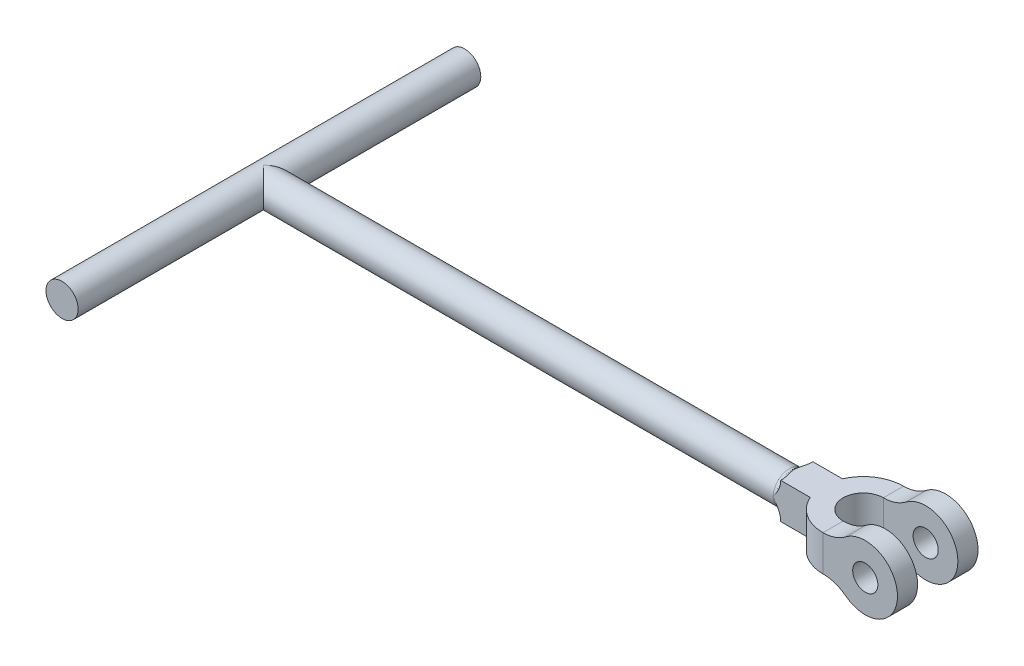
SolidWorks part; units mm, degrees
ref_plane "Front Plane" through (0, 0, 0) normal (0, 0, 1) x (1, 0, 0)
ref_plane "Top Plane" through (0, 0, 0) normal (0, 1, 0) x (1, 0, 0)
ref_plane "Right Plane" through (0, 0, 0) normal (1, 0, 0) x (0, 0, -1)
sketch "Sketch1" plane through (0, 0, 0) normal (0, 1, 0) x (1, 0, 0)
  line L0 (0, 40) -> (0, 20)
  line L1 (0, -20) -> (0, -40)
  line L2 (-80.9651, 0) -> (54.4772, 0) construction
  line L3 (-36.6606, 16) -> (-66, 16)
  line L4 (-36.6606, -16) -> (-66, -16)
  line L5 (74, 43.4733) -> (74, -48.5878) construction
  line L6 (-66, 16) -> (-66, -16)
  arc A0 (0, 20) -> (0, -20) centre (0, 0) ccw
  arc A1 (0, 40) -> (-36.6606, 16) centre (0, 0) ccw
  arc A2 (-36.6606, -16) -> (0, -40) centre (0, 0) ccw
  dimension "D1" = 20
  dimension "D2" = 40
  dimension "D3" = 16
  dimension "D4" = 16
  dimension "D5" = 74
  dimension "D6" = 140
  dimension "D7" = 140
extrude "Boss-Extrude1" add sketch "Sketch1" along normal blind 35.5
sketch "Sketch2" plane through (-66, 0, 0) normal (-1, 0, 0) x (0, 0, 1)
  line L3 (16, 35.5) -> (16, 0) construction
  circle A1 centre (0, 17.75) radius 16
  point P5 (16, 17.75)
  dimension "D1" = 32
extrude "Boss-Extrude2" add sketch "Sketch2" along normal blind 30
fillet "Fillet6" radius 7.5 1 edges at (-66, 33.75, 0) type face fillet first side face at (-66, 30.625, 0) second side face at (-96, 17.75, 16)
fillet "Fillet7" radius 7.5 3 edges at (-66, 1.75, 0) (-69.75, 17.75, 16) (-69.75, 17.75, -16)
ref_plane "Plane2" through (0, 0, 40) normal (0, 0, 1) x (1, 0, 0)
sketch "Sketch3" plane through (0, 0, 40) normal (0, 0, 1) x (1, 0, 0)
  line L0 (-36.6606, 0) -> (0, 0) construction
  line L1 (0, 35.5) -> (-36.6606, 35.5) construction
  line L2 (0, 35.5) -> (0, 0) construction
  line L3 (-36.6606, 0) -> (0, 0)
  line L4 (0, 35.5) -> (-36.6606, 35.5)
  line L5 (0, 35.5) -> (0, 0)
  line L6 (42, 40.978) -> (42, -11.3272)
  line L7 (0, 17.75) -> (87.3676, 17.75) construction
  line L8 (0, 35.5) -> (0, 0)
  circle A0 centre (42, 17.75) radius 12.5
  circle A1 centre (42, 17.75) radius 32
  arc A2 (0, 35.5) -> (22.5273, 43.1432) centre (0, 72.5197) ccw
  arc A3 (0, 0) -> (22.5273, -7.6432) centre (0, -37.0197) cw
  point P6 (42, 14.8254)
  dimension "D2" = 64
  dimension "D3" = 25
  dimension "D1" = 42
extrude "Boss-Extrude3" add sketch "Sketch3" against normal blind 20
mirror "Mirror1" about plane through (0, 0, 0) normal (0, 0, 1) of "Boss-Extrude3"
sketch "Sketch4" plane through (-96, 0, 0) normal (-1, 0, 0) x (0, 0, 1)
  line L0 (0, -4.3746) -> (0, 47.0287) construction
  circle A0 centre (0, 17.75) radius 16
  circle A1 centre (0, 17.75) radius 16 construction
extrude "Boss-Extrude4" add sketch "Sketch4" along normal blind 500
sketch "Sketch6" plane through (0, 0, 0) normal (0, 0, 1) x (1, 0, 0)
  line L0 (-638.5393, 17.75) -> (-551.4731, 17.75) construction
  line L1 (-596, 33.75) -> (-596, 1.75) construction
  line L2 (-596, 17.75) -> (-73.5, 17.75) construction
  circle A0 centre (-596, 17.75) radius 16
  dimension "D1" = 32
extrude "Boss-Extrude6" add sketch "Sketch6" along normal mid plane 400
